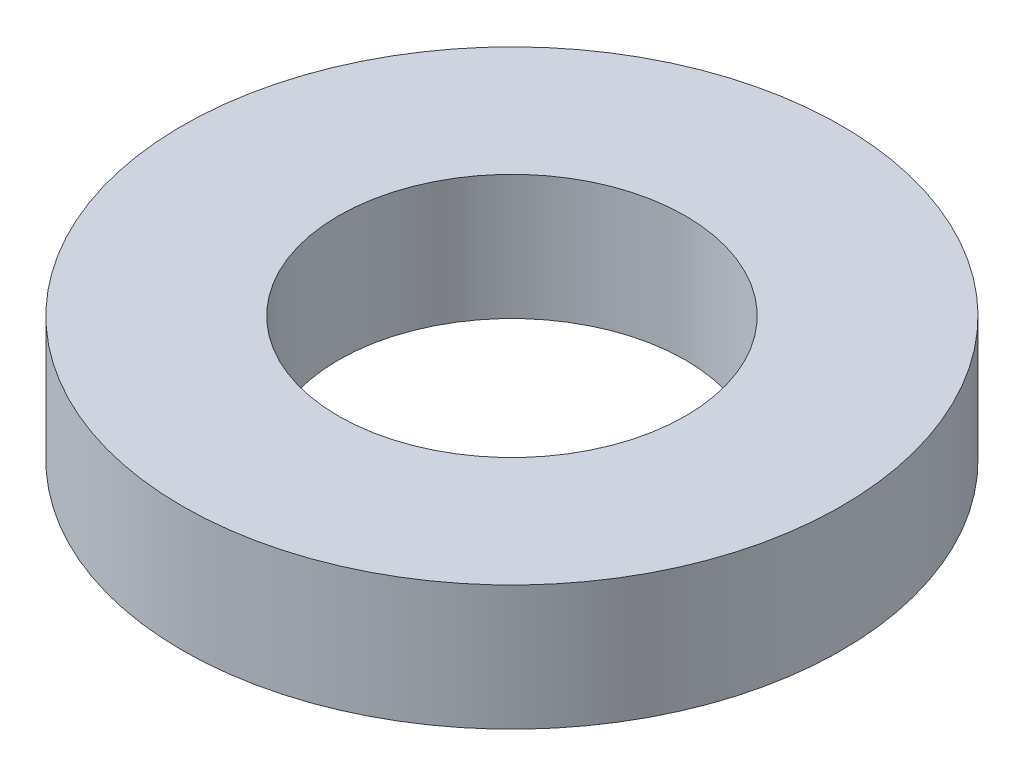
SolidWorks part; units mm, degrees
ref_plane "Front Plane" through (0, 0, 0) normal (0, 0, 1) x (1, 0, 0)
ref_plane "Top Plane" through (0, 0, 0) normal (0, 1, 0) x (1, 0, 0)
ref_plane "Right Plane" through (0, 0, 0) normal (1, 0, 0) x (0, 0, -1)
sketch "Sketch1" plane through (0, 0, 0) normal (0, 1, 0) x (1, 0, 0)
  circle A0 centre (0, 0) radius 47.5
  dimension "FLANGE_OD" = 95
extrude "Boss-Extrude1" add sketch "Sketch1" along normal blind 18
sketch "Sketch2" plane through (0, 0, 0) normal (0, 1, 0) x (1, 0, 0)
  circle A0 centre (0, 0) radius 25
  dimension "BORE_D" = 50
extrude "Cut-Extrude1" cut sketch "Sketch2" along normal through all
sketch "Sketch3" plane through (0, 18, 0) normal (0, 1, 0) x (1, 0, 0)
  circle A0 centre (0, 0) radius 18.4788 construction
  circle A1 centre (-18.4788, 0) radius 3.5575
  dimension "BOLT_D" = 7.1151
  dimension "BOLT_PCD" = 36.9576
extrude "Cut-Extrude2" cut sketch "Sketch3" against normal blind 17.8604 rebuild error yes
pattern_circular "CirPattern1" count 5 over 360 rebuild error yes
